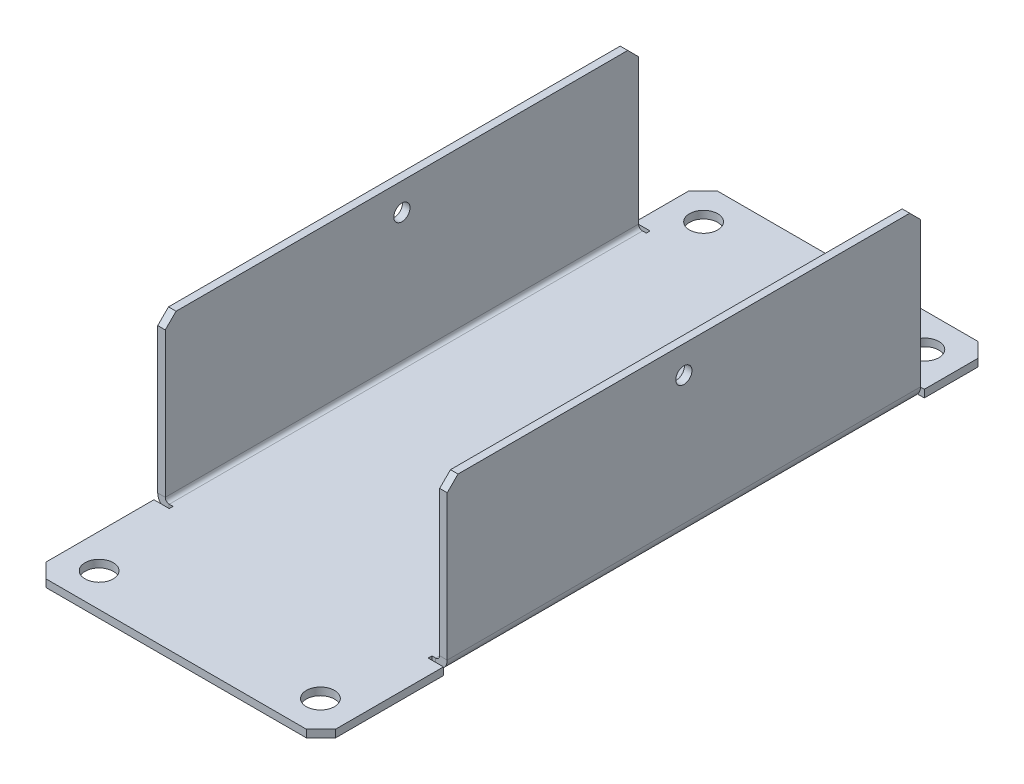
SolidWorks part; units mm, degrees
note: The reader was unsure of these and kept them because the rebuilt part matched: flange length of "Edge-Flange2".
ref_plane "Front Plane" through (0, 0, 0) normal (0, 0, 1) x (1, 0, 0)
ref_plane "Top Plane" through (0, 0, 0) normal (0, 1, 0) x (1, 0, 0)
ref_plane "Right Plane" through (0, 0, 0) normal (1, 0, 0) x (0, 0, -1)
sketch "Sketch1" plane through (0, 0, 0) normal (0, 1, 0) x (1, 0, 0)
  line L1 (-26.825, 62.225) -> (26.825, 62.225)
  line L2 (-26.825, 62.225) -> (-26.825, -62.225)
  line L3 (-26.825, -62.225) -> (26.825, -62.225)
  line L4 (26.825, 62.225) -> (26.825, -62.225)
  line L5 (-26.825, 62.225) -> (26.825, -62.225) construction
  line L6 (-26.825, -62.225) -> (26.825, 62.225) construction
  line L7 (-20.5, -56) -> (20.5, -56) construction
  line L8 (-20.5, -56) -> (-20.5, 56) construction
  line L9 (-20.5, 56) -> (20.5, 56) construction
  line L10 (20.5, -56) -> (20.5, 56) construction
  line L11 (-20.5, -56) -> (20.5, 56) construction
  line L12 (-20.5, 56) -> (20.5, -56) construction
  circle A0 centre (-20.5, 56) radius 2.61
  circle A1 centre (20.5, 56) radius 2.61
  circle A2 centre (20.5, -56) radius 2.61
  circle A3 centre (-20.5, -56) radius 2.61
  point P0 (0, 0)
  point P5 (0, 0)
  dimension "D5" = 5.22
  dimension "D1" = 124.45
  dimension "D2" = 53.65
  dimension "D3" = 112
  dimension "D4" = 41
base flange "Base-Flange1" sketch "Sketch1" thickness 1.4 reverse thickness direction no parameters "D1"=0.7366
chamfer "Chamfer1" distance 2.7 angle 45 4 edges at (-26.825, -0.7, -62.225) (26.825, -0.7, -62.225) (-26.825, -0.7, 62.225) (26.825, -0.7, 62.225)
edge flange "Edge-Flange2" sketch "Sketch13" flange profiles "Sketch13", "Sketch15" flange angle 90 flange length 29.6 flange position material inside bend radius 0.7366 thickness 1.4 relief rectangular parameters "D6"=10, "D8"=1
sketch "Sketch13" plane through (26.825, 0, 0) normal (1, 0, 0) x (0, 0, -1)
  line L2 (-38.825, 0) -> (-38.825, 29.6)
  line L3 (-38.825, 29.6) -> (48.875, 29.6)
  line L4 (48.875, 29.6) -> (48.875, 0)
  line L5 (-59.525, 0) -> (59.525, 0) construction
  line L6 (-38.825, 0) -> (48.875, 0)
  line L7 (5.025, 0) -> (5.025, 67.1952) construction
  line L8 (-62.225, -1.4) -> (-62.225, 0) construction
  point P8 (0, 0)
  point P9 (0.1518, 0.0545)
  point P11 (5.025, 0)
  point P15 (-62.225, -0.7)
  dimension "D1" = 87.7
  dimension "D2" = 23.4
sketch "Sketch15" plane through (-26.825, 0, 0) normal (-1, 0, 0) x (0, 0, 1)
  line L0 (-59.525, 0) -> (59.525, 0) construction
  line L1 (-48.875, 0) -> (38.825, 0)
  line L2 (-48.875, 0) -> (-48.875, 29.6)
  line L3 (-48.875, 29.6) -> (38.825, 29.6)
  line L4 (38.825, 29.6) -> (38.825, 0)
  line L5 (-5.025, 0) -> (-5.025, 39.7185) construction
  line L6 (-5.025, 0) -> (-5.025, 67.1952) construction
  dimension "D1" = 87.7
bend "EdgeBend3" bend radius 0.7366 bend angle 90 parameters "D5"=1
bend "EdgeBend4" bend radius 0.7366 bend angle 90 parameters "D5"=3
chamfer "Chamfer2" distance 2 angle 45 4 edges at (26.125, 29.6, -48.875) (-26.125, 29.6, -48.875) (26.125, 29.6, 38.825) (-26.125, 29.6, 38.825)
sketch "Sketch18" plane through (26.825, 0, 0) normal (1, 0, 0) x (0, 0, -1)
  circle A0 centre (5.025, 24.54) radius 1.5
extrude "Cut-Extrude1" cut sketch "Sketch18" against normal through all normal cut yes
sketch "Bend-Lines1" [suppressed] plane through (0, 0, 0) normal (0, 1, 0) x (1, 0, 0)
sketch "Bounding-Box1" [suppressed] plane through (0, 0, 0) normal (0, 1, 0) x (1, 0, 0)
sheet metal parameters "Sheet-Metal1" thickness 1.4 parameters "D1"=0.7366
flat pattern "Flat-Pattern1" [suppressed]
sketch "Bend-Lines2" plane through (0, 0, 0) normal (0, 1, 0) x (1, 0, 0)
sketch3d "Bounding-Box2" [suppressed]
  line L0 (-26.825, 62.225, 0) -> (-26.825, -62.225, 0) construction
  line L1 (26.825, 62.225, 0) -> (26.825, -62.225, 0) construction
  line L2 (-26.825, 62.225, 0) -> (26.825, 62.225, 0) construction
  line L3 (-26.825, -62.225, 0) -> (26.825, -62.225, 0) construction
sheet metal parameters "Sheet-Metal3" thickness 1.4 parameters "D1"=0.7366
flat pattern "Flat-Pattern1"
sketch "Bend-Lines2" plane through (0, 0, 0) normal (0, 1, 0) x (1, 0, 0)
  line L0 (25.8167, -38.825) -> (25.8167, 48.875) construction
  line L1 (25.8167, -38.825) -> (25.8167, 48.875) construction
  line L2 (-25.8167, 48.875) -> (-25.8167, -38.825) construction
  line L3 (-25.8167, 48.875) -> (-25.8167, -38.825) construction
sketch3d "Bounding-Box2" [suppressed]
  line L0 (-55.8084, 62.225, 0) -> (-55.8084, -62.225, 0) construction
  line L1 (55.8084, 62.225, 0) -> (55.8084, -62.225, 0) construction
  line L2 (-55.8084, 62.225, 0) -> (55.8084, 62.225, 0) construction
  line L3 (-55.8084, -62.225, 0) -> (55.8084, -62.225, 0) construction
bend of the flat pattern "Flatten-<EdgeBend3>1"
bend of the flat pattern "Flatten-<EdgeBend4>1"
sheet metal parameters "Sheet-Metal4" thickness 1.4 parameters "D1"=0.7366
flat pattern "Flat-Pattern1"
sketch "Bend-Lines2" plane through (0, 0, 0) normal (0, 1, 0) x (1, 0, 0)
  line L0 (25.8167, -38.825) -> (25.8167, 48.875) construction
  line L1 (25.8167, -38.825) -> (25.8167, 48.875) construction
  line L2 (-25.8167, 48.875) -> (-25.8167, -38.825) construction
  line L3 (-25.8167, 48.875) -> (-25.8167, -38.825) construction
sketch3d "Bounding-Box2" [suppressed]
  line L0 (-55.8084, 62.225, 0) -> (-55.8084, -62.225, 0) construction
  line L1 (55.8084, 62.225, 0) -> (55.8084, -62.225, 0) construction
  line L2 (-55.8084, 62.225, 0) -> (55.8084, 62.225, 0) construction
  line L3 (-55.8084, -62.225, 0) -> (55.8084, -62.225, 0) construction
bend of the flat pattern "Flatten-<EdgeBend3>1"
bend of the flat pattern "Flatten-<EdgeBend4>1"
